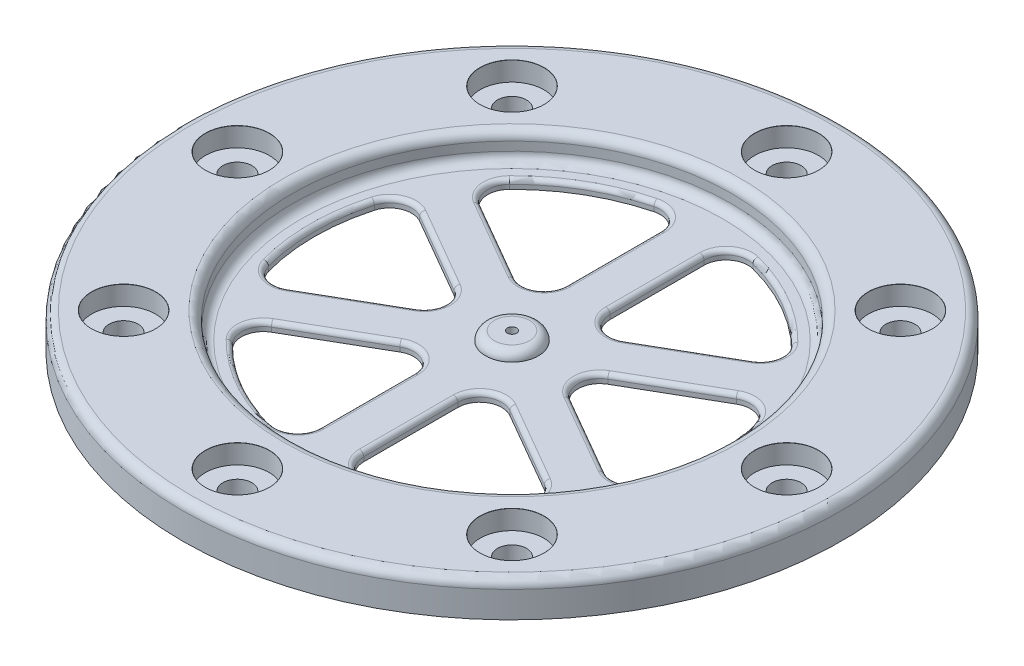
SolidWorks part; units mm, degrees
ref_plane "Front Plane" through (0, 0, 0) normal (0, 0, 1) x (1, 0, 0)
ref_plane "Top Plane" through (0, 0, 0) normal (0, 1, 0) x (1, 0, 0)
ref_plane "Right Plane" through (0, 0, 0) normal (1, 0, 0) x (0, 0, -1)
sketch "Sketch1" plane through (0, 0, 0) normal (0, 1, 0) x (1, 0, 0)
  circle A0 centre (0, 0) radius 75
  dimension "D1" = 150
extrude "Boss-Extrude1" add sketch "Sketch1" along normal blind 8
sketch "Sketch2" plane through (0, 8, 0) normal (0, 1, 0) x (1, 0, 0)
  circle A3 centre (0, 0) radius 50
  circle A4 centre (0, 0) radius 50
  dimension "D1" = 25
extrude "Cut-Extrude1" cut sketch "Sketch2" against normal offset from surface (6 mm away) 2 up to face at (0, 0, 75)
sketch "Sketch3" plane through (0, 2, 0) normal (0, 1, 0) x (1, 0, 0)
  line L0 (0, 17.3205) -> (0, 38.7298)
  line L1 (-15, 8.6603) -> (-33.541, 19.3649)
  line L2 (-5, 17.3205) -> (-5, 38.7298)
  line L3 (-12.5, 12.9904) -> (-31.041, 23.695)
  circle A0 centre (0, 0) radius 50 construction
  circle A1 centre (0, 0) radius 50 construction
  arc A3 (-12.5, 48.4123) -> (-35.6763, 35.0315) centre (0, 0) ccw
  arc A4 (0, 17.3205) -> (-15, 8.6603) centre (-10, 17.3205) cw
  arc A5 (-33.541, 19.3649) -> (-35.6763, 35.0315) centre (-28.541, 28.0252) cw
  arc A6 (0, 38.7298) -> (-12.5, 48.4123) centre (-10, 38.7298) ccw
  arc A7 (-31.041, 23.695) -> (-32.1086, 31.5283) centre (-28.541, 28.0252) cw
  arc A8 (-11.25, 43.5711) -> (-32.1086, 31.5283) centre (0, 0) ccw
  arc A9 (-5, 38.7298) -> (-11.25, 43.5711) centre (-10, 38.7298) ccw
  arc A10 (-5, 17.3205) -> (-12.5, 12.9904) centre (-10, 17.3205) cw
  point P11 (0, 0)
  point P14 (-43.3013, 25)
  point P17 (0, 50)
  dimension "D2" = 10
  dimension "D1" = 60
  dimension "D3" = 5
extrude "Cut-Extrude2" cut sketch "Sketch3" against normal through all contours A10 L2 A9 A8 A7 L3 region at (-16.391, 2, -28.3901)
fillet "Fillet2" radius 1 6 edges at (-7.5, 2, -12.9904) (-5, 2, -28.0252) (-6.9381, 2, -42.6827) (-22.5, 2, -38.9711) (-33.4952, 2, -27.3499) (-21.7705, 2, -18.3427)
pattern_circular "CirPattern1" count 6 over 360 about axis through (0, 8, 0) along (0, -1, 0) of "Cut-Extrude2", "Fillet2" reverse direction yes
sketch "Sketch4" plane through (0, 2, 0) normal (0, 1, 0) x (1, 0, 0)
  circle A0 centre (0, 0) radius 6
  circle A1 centre (0, 0) radius 1.05
  dimension "D1" = 12
  dimension "D2" = 2.1
extrude "Boss-Extrude2" add sketch "Sketch4" along normal blind 2 contours A0 A1 region at (-5.8303, 2, 0)
sketch "Sketch5" plane through (0, 4, 0) normal (0, 1, 0) x (1, 0, 0)
  circle A0 centre (0, 0) radius 1.05 construction
  circle A1 centre (0, 0) radius 1.05
  dimension "D1" = 2.1
extrude "Cut-Extrude3" cut sketch "Sketch5" against normal through all and the other way through all
sketch "Sketch6" plane through (0, 8, 0) normal (0, 1, 0) x (1, 0, 0)
  line L0 (0, 0) -> (0, 62.5) construction
  circle A0 centre (0, 62.5) radius 7.5
  dimension "D2" = 15
  dimension "D1" = 62.5
fillet "Fillet1" radius 2 3 edges at (0, 4, 6) (0, 8, 75) (0, 8, 50)
fillet "Fillet3" radius 2 1 edges at (0, 2, 50)
hole_wizard "CBORE for M6 Hex Head Bolt2" positions "Sketch19" profile "Sketch20" counterbore size "M6" standard "ANSI Metric" end condition through all
sketch "Sketch19" plane through (0, 8, 0) normal (0, 1, 0) x (1, 0, 0)
  line L2 (-3.3, 62.5) -> (3.3, 62.5) construction
  point P0 (0, 62.5)
  dimension "D1" = 6.6
sketch "Sketch20" plane through (0, 8, -62.5) normal (1, 0, 0) x (0, 0, 1)
  line L0 (0, 0) -> (0, 8)
  line L1 (0, 8) -> (3.3, 8)
  line L3 (3.3, 8) -> (3.3, 4.38)
  line L4 (7.275, 4.38) -> (3.3, 4.38)
  line L5 (7.275, 4.38) -> (7.275, 0.025)
  line L6 (7.275, 0.025) -> (7.3, 0)
  line L7 (7.3, 0) -> (0, 0)
  line L8 (-7.275, 0.025) -> (-7.3, 0) construction
  line L11 (0, -6.35) -> (0, 107.95) construction
  dimension "Thru Hole Dia." = 6.6
  dimension "Thru Hole Depth" = 8
  dimension "C'Bore Dia." = 14.55
  dimension "C'Bore Depth" = 4.38
  dimension "Near C'Sink Dia." = 14.6
  dimension "Near C'Sink Angle" = 90
pattern_circular "CirPattern2" count 8 over 360 about axis through (0, 8, 0) along (0, 1, 0) of "CBORE for M6 Hex Head Bolt2"
